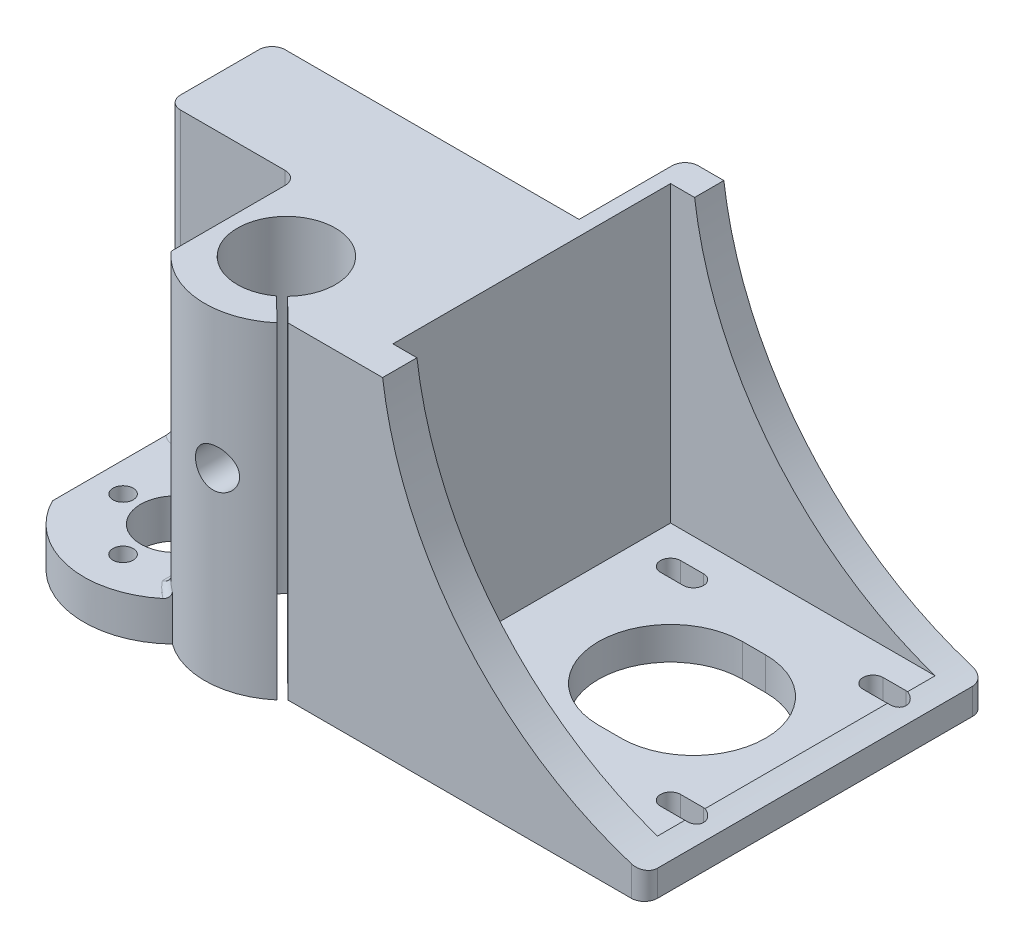
SolidWorks part; units mm, degrees
ref_plane "Alzado" through (0, 0, 0) normal (0, 0, 1) x (1, 0, 0)
ref_plane "Planta" through (0, 0, 0) normal (0, 1, 0) x (1, 0, 0)
ref_plane "Vista lateral" through (0, 0, 0) normal (1, 0, 0) x (0, 0, -1)
sketch "Croquis2" plane through (0, 0, 0) normal (0, 1, 0) x (1, 0, 0)
  line L0 (12.5, 12.7) -> (12.5, 28.7) construction
  line L1 (0, 0) -> (93, 0)
  line L2 (0, 0) -> (0, 48)
  line L3 (0, 48) -> (47, 48)
  line L4 (93, 0) -> (93, 48)
  line L7 (93, 48) -> (93, 64.23)
  line L8 (93, 64.23) -> (47, 64.23)
  line L9 (47, 48) -> (47, 64.23)
  circle A0 centre (29.5, 20.7) radius 7.5
  circle A1 centre (12.5, 20.7) radius 5.3
  circle A2 centre (12.5, 20.7) radius 8 construction
  circle A3 centre (12.5, 12.7) radius 1.55
  circle A4 centre (4.5, 20.7) radius 1.55
  circle A5 centre (12.5, 28.7) radius 1.55
  dimension "D3" = 15
  dimension "D4" = 10.6
  dimension "D9" = 16
  dimension "D10" = 3.1
  dimension "D1" = 93
  dimension "D2" = 48
  dimension "D5" = 17
  dimension "D6" = 20.7
  dimension "D7" = 20.7
  dimension "D8" = 29.5
  dimension "D11" = 46
  dimension "D12" = 48
  dimension "D13" = 64.23
extrude "Saliente-Extruir1" add sketch "Croquis2" along normal blind 50
sketch "Croquis3" plane through (0, 50, 0) normal (0, 1, 0) x (1, 0, 0)
  line L0 (47, 48) -> (0, 48) construction
  line L1 (0, 0) -> (20, 0)
  line L2 (0, 0) -> (0, 32)
  line L3 (0, 32) -> (20, 32)
  line L4 (20, 0) -> (20, 32)
  circle A0 centre (29.5, 20.7) radius 9.5 construction
  dimension "D1" = 19
  dimension "D2" = 16
extrude "Cortar-Extruir1" cut sketch "Croquis3" against normal blind 44
sketch "Croquis8" plane through (0, 0, 0) normal (0, -1, 0) x (1, 0, 0)
  line L0 (55, -54) -> (86, -23) construction
  line L1 (0, 0) -> (93, 0) construction
  line L2 (58.5, -23) -> (55, -23) construction
  line L3 (93, 0) -> (93, -64.23) construction
  line L4 (58.5, -24.55) -> (55, -24.55)
  line L5 (58.5, -21.45) -> (55, -21.45)
  line L6 (86, -23) -> (89.5, -23) construction
  line L7 (86, -21.45) -> (89.5, -21.45)
  line L8 (86, -24.55) -> (89.5, -24.55)
  line L9 (55, -54) -> (58.5, -54) construction
  line L10 (55, -52.45) -> (58.5, -52.45)
  line L11 (55, -55.55) -> (58.5, -55.55)
  line L12 (86, -54) -> (89.5, -54) construction
  line L13 (86, -52.45) -> (89.5, -52.45)
  line L14 (86, -55.55) -> (89.5, -55.55)
  line L15 (70.5, -38.5) -> (74, -38.5) construction
  line L16 (70.5, -27.45) -> (74, -27.45)
  line L17 (70.5, -49.55) -> (74, -49.55)
  circle A0 centre (55, -23) radius 1.55 construction
  circle A1 centre (86, -23) radius 1.55 construction
  circle A2 centre (55, -54) radius 1.55 construction
  circle A3 centre (86, -54) radius 1.55 construction
  circle A4 centre (70.5, -38.5) radius 11.05 construction
  arc A5 (58.5, -24.55) -> (58.5, -21.45) centre (58.5, -23) ccw
  arc A6 (55, -21.45) -> (55, -24.55) centre (55, -23) ccw
  arc A7 (86, -21.45) -> (86, -24.55) centre (86, -23) ccw
  arc A8 (89.5, -24.55) -> (89.5, -21.45) centre (89.5, -23) ccw
  arc A9 (55, -52.45) -> (55, -55.55) centre (55, -54) ccw
  arc A10 (58.5, -55.55) -> (58.5, -52.45) centre (58.5, -54) ccw
  arc A11 (86, -52.45) -> (86, -55.55) centre (86, -54) ccw
  arc A12 (89.5, -55.55) -> (89.5, -52.45) centre (89.5, -54) ccw
  arc A13 (70.5, -27.45) -> (70.5, -49.55) centre (70.5, -38.5) ccw
  arc A14 (74, -49.55) -> (74, -27.45) centre (74, -38.5) ccw
  point P13 (56.75, -23)
  point P20 (56.75, -54)
  point P21 (87.75, -23)
  point P32 (87.75, -54)
  point P38 (72.25, -38.5)
  dimension "D1" = 3.1
  dimension "D3" = 31
  dimension "D4" = 31
  dimension "D7" = 38
  dimension "D8" = 22.1
  dimension "D10" = 38
  dimension "D13" = 3.5
  dimension "D2" = 31
  dimension "D5" = 31
  dimension "D6" = 23
  dimension "D9" = 23
  dimension "D11" = 3.1
  dimension "D12" = 3.5
  dimension "D14" = 3.5
  dimension "D15" = 3.5
  dimension "D16" = 22.1
  dimension "D17" = 3.5
extrude "Cortar-Extruir2" cut sketch "Croquis8" against normal up to surface (50 mm away) up to face at (40, 50, -36.0575)
sketch "Croquis9" plane through (0, 0, 0) normal (-1, 0, 0) x (0, 0, 1)
  line L0 (-48, 50) -> (-48, 0) construction
  line L5 (-48, 50) -> (-32, 50) construction
  line L7 (-35.5, 35) -> (-43.25, 35)
  line L8 (-35.5, 35) -> (-35.5, 22.7)
  line L9 (-35.5, 22.7) -> (-43.25, 22.7)
  line L10 (-43.25, 35) -> (-43.25, 22.7)
  dimension "D1" = 7.75
  dimension "D2" = 12.3
  dimension "D3" = 4.75
  dimension "D4" = 15
extrude "Cortar-Extruir3" cut sketch "Croquis9" against normal blind 43
sketch "Croquis10" plane through (0, 0, -43.25) normal (0, 0, 1) x (1, 0, 0)
  line L0 (43, 35) -> (43, 22.7) construction
  line L1 (43, 35) -> (0, 35) construction
  circle A0 centre (31, 28.85) radius 1.55
  circle A1 centre (6, 28.85) radius 1.55
  dimension "D1" = 3.1
  dimension "D2" = 25
  dimension "D3" = 12
  dimension "D4" = 6.15
  dimension "D5" = 6.15
extrude "Cortar-Extruir4" cut sketch "Croquis10" against normal through all and the other way through all
sketch "Croquis11" plane through (0, 0, -48) normal (0, 0, -1) x (-1, 0, 0)
  line L1 (-9.3453, 28.9998) -> (-7.8024, 26.0278)
  line L2 (-7.8024, 26.0278) -> (-4.4571, 25.878)
  line L3 (-4.4571, 25.878) -> (-2.6547, 28.7002)
  line L4 (-2.6547, 28.7002) -> (-4.1976, 31.6722)
  line L5 (-4.1976, 31.6722) -> (-7.5429, 31.822)
  line L6 (-7.5429, 31.822) -> (-9.3453, 28.9998)
  line L7 (-34.3453, 28.9998) -> (-32.8024, 26.0278)
  line L8 (-32.8024, 26.0278) -> (-29.4571, 25.878)
  line L9 (-29.4571, 25.878) -> (-27.6547, 28.7002)
  line L10 (-27.6547, 28.7002) -> (-29.1976, 31.6722)
  line L11 (-29.1976, 31.6722) -> (-32.5429, 31.822)
  line L12 (-32.5429, 31.822) -> (-34.3453, 28.9998)
  circle A0 centre (-6, 28.85) radius 2.9 construction
  circle A1 centre (-31, 28.85) radius 2.9 construction
  dimension "D1" = 5.8
  dimension "D2" = 5.8
extrude "Cortar-Extruir5" cut sketch "Croquis11" against normal blind 2.5
sketch "Croquis12" plane through (0, 0, 0) normal (0, 0, 1) x (1, 0, 0)
  circle A1 centre (31, 28.85) radius 3
  dimension "D1" = 6
extrude "Cortar-Extruir6" cut sketch "Croquis12" against normal blind 32
sketch "Croquis13" plane through (0, 50, 0) normal (0, 1, 0) x (1, 0, 0)
  line L0 (93, 64.23) -> (47, 64.23) construction
  line L1 (91.75, 59.75) -> (49.25, 59.75)
  line L2 (91.75, 59.75) -> (91.75, 17.25)
  line L3 (91.75, 17.25) -> (49.25, 17.25)
  line L4 (49.25, 59.75) -> (49.25, 17.25)
  line L5 (93, 0) -> (93, 64.23) construction
  dimension "D1" = 42.5
  dimension "D2" = 42.5
  dimension "D3" = 4.48
  dimension "D4" = 1.25
extrude "Cortar-Extruir7" cut sketch "Croquis13" against normal blind 45
sketch "Croquis14" plane through (0, 0, 0) normal (0, -1, 0) x (1, 0, 0)
  line L1 (93, 0) -> (93, -64.23) construction
  line L2 (93, -12) -> (38.4755, -12)
  line L3 (93, -12) -> (93, 0)
  line L4 (93, 0) -> (0, 0)
  line L5 (0, -14.3952) -> (0, 0)
  arc A2 (38.4755, -12) -> (22.1691, -10.5754) centre (29.5, -20.7) ccw
  arc A4 (22.1691, -10.5754) -> (0, -14.3952) centre (12.5, -20.7) ccw
  dimension "D2" = 28
  dimension "D4" = 25
  dimension "D3" = 12
extrude "Cortar-Extruir8" cut sketch "Croquis14" against normal up to surface (50 mm away) up to face at (70.5, 50, -38.5)
fillet "Redondeo1" radius 2 4 edges at (47, 25, -64.23) (0, 25, -48) (20, 28, -32) (0, 28, -32)
sketch "Croquis15" plane through (0, 0, -12) normal (0, 0, 1) x (1, 0, 0)
  line L0 (38.4755, 0) -> (93, 0) construction
  line L1 (93, 50) -> (52.928, 50)
  line L2 (93, 50) -> (93, 4)
  arc A0 (93, 4) -> (52.928, 50) centre (107.5482, 57.1274) cw
  dimension "D1" = 4
extrude "Cortar-Extruir9" cut sketch "Croquis15" against normal up to surface (52.23 mm away) up to face at (71, 25, -64.23)
fillet "Redondeo2" radius 2 2 edges at (93, 2, -64.23) (93, 2, -12)
sketch "Croquis16" plane through (0, 50, 0) normal (0, 1, 0) x (1, 0, 0)
  line L0 (20, 8.8784) -> (20, 30) construction
  line L1 (20, 8.8784) -> (20, 12.576)
  arc A0 (20, 12.576) -> (22.1691, 10.5754) centre (29.5, 20.7) ccw
  arc A1 (20, 8.8784) -> (22.1691, 10.5754) centre (12.5, 20.7) ccw construction
  arc A2 (20, 8.8784) -> (22.1691, 10.5754) centre (12.5, 20.7) ccw
extrude "Cortar-Extruir10" cut sketch "Croquis16" against normal up to surface (44 mm away) up to face at (12.5, 6, -26)
sketch "Croquis17" plane through (0, 0, 0) normal (0, -1, 0) x (1, 0, 0)
  line L0 (38.4755, -12) -> (34.8853, -15.48)
  line L1 (37.5989, -11.1785) -> (33.9807, -14.6856)
  circle A0 centre (29.5, -20.7) radius 7.5 construction
  circle A1 centre (29.5, -20.7) radius 7.5
  arc A2 (38.4755, -12) -> (22.1691, -10.5754) centre (29.5, -20.7) ccw construction
  arc A3 (38.4755, -12) -> (22.1691, -10.5754) centre (29.5, -20.7) ccw
  arc M9 (38.4755, -12) -> (22.1691, -10.5754) centre (29.5, -20.7) ccw
  circle M23 centre (29.5, -20.7) radius 7.5
  dimension "D1" = 1.2
extrude "Cortar-Extruir11" cut sketch "Croquis17" against normal up to surface (50 mm away) contours L1 L0 M9 M23 region at (36.2438, 0, -13.3265) up to face at (29.5, 50, -13.2)
fillet "Redondeo3" radius 1 5 edges at (0.5858, 6, -32.5858) (10, 6, -32) (19.4142, 6, -31.4142) (21.0253, 6, -11.5114) (20, 6, -21.288)
